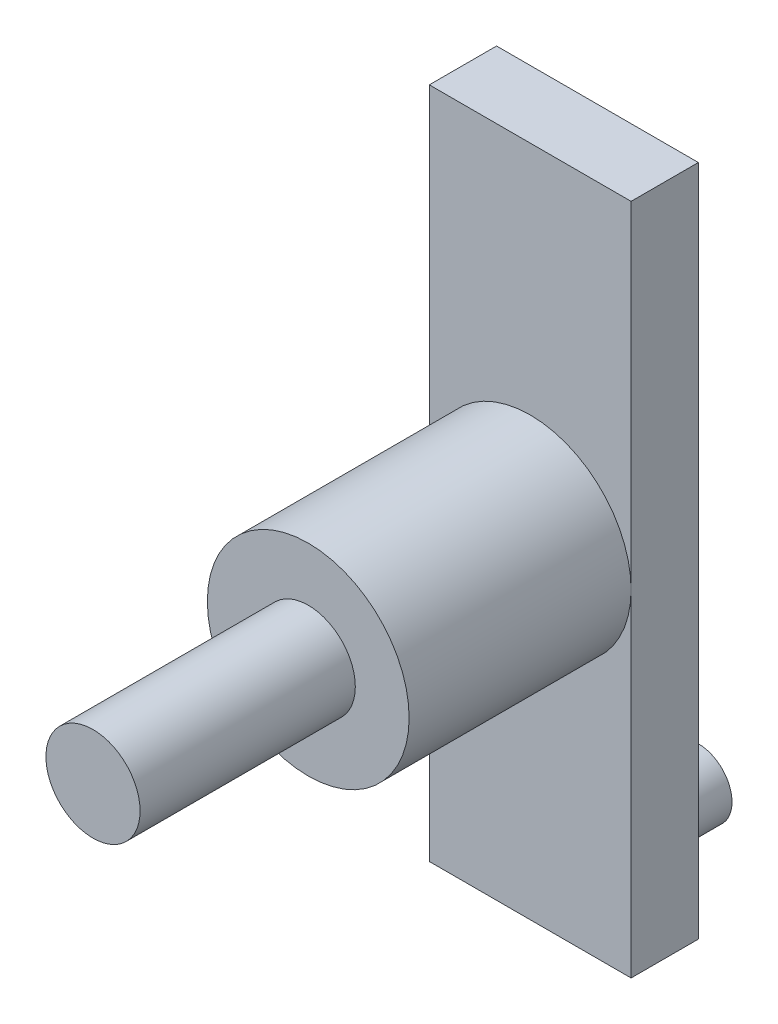
SolidWorks part; units mm, degrees
ref_plane "Front Plane" through (0, 0, 0) normal (0, 0, 1) x (1, 0, 0)
ref_plane "Top Plane" through (0, 0, 0) normal (0, 1, 0) x (1, 0, 0)
ref_plane "Right Plane" through (0, 0, 0) normal (1, 0, 0) x (0, 0, -1)
sketch "Sketch1" plane through (0, 0, 0) normal (0, 0, 1) x (1, 0, 0)
  circle A0 centre (0, 0) radius 7
  circle A1 centre (0, 0) radius 15
  dimension "D1" = 30
  dimension "D2" = 14
extrude "Boss-Extrude1" add sketch "Sketch1" along normal blind 65 contours A0 region at (0, 0, 0)
extrude "Boss-Extrude2" add sketch "Sketch1<3>" along normal blind 33
sketch "Sketch1<3>" plane through (0, 0, 0) normal (0, 0, 1) x (1, 0, 0) same geometry as "Sketch1"
sketch "Sketch3" plane through (0, 0, 0) normal (0, 0, -1) x (-1, 0, 0)
  line L1 (15, 50) -> (-15, 50)
  line L2 (15, 50) -> (15, -50)
  line L3 (15, -50) -> (-15, -50)
  line L4 (-15, 50) -> (-15, -50)
  line L5 (15, 50) -> (-15, -50) construction
  line L6 (15, -50) -> (-15, 50) construction
  point P0 (0, 0)
  dimension "D1" = 30
  dimension "D2" = 100
extrude "Boss-Extrude4" add sketch "Sketch3" along normal blind 10
sketch "Sketch4" plane through (0, 0, -10) normal (0, 0, -1) x (-1, 0, 0)
  circle A0 centre (0, -44.8339) radius 5
  dimension "D1" = 10
extrude "Boss-Extrude5" add sketch "Sketch4" along normal blind 15
